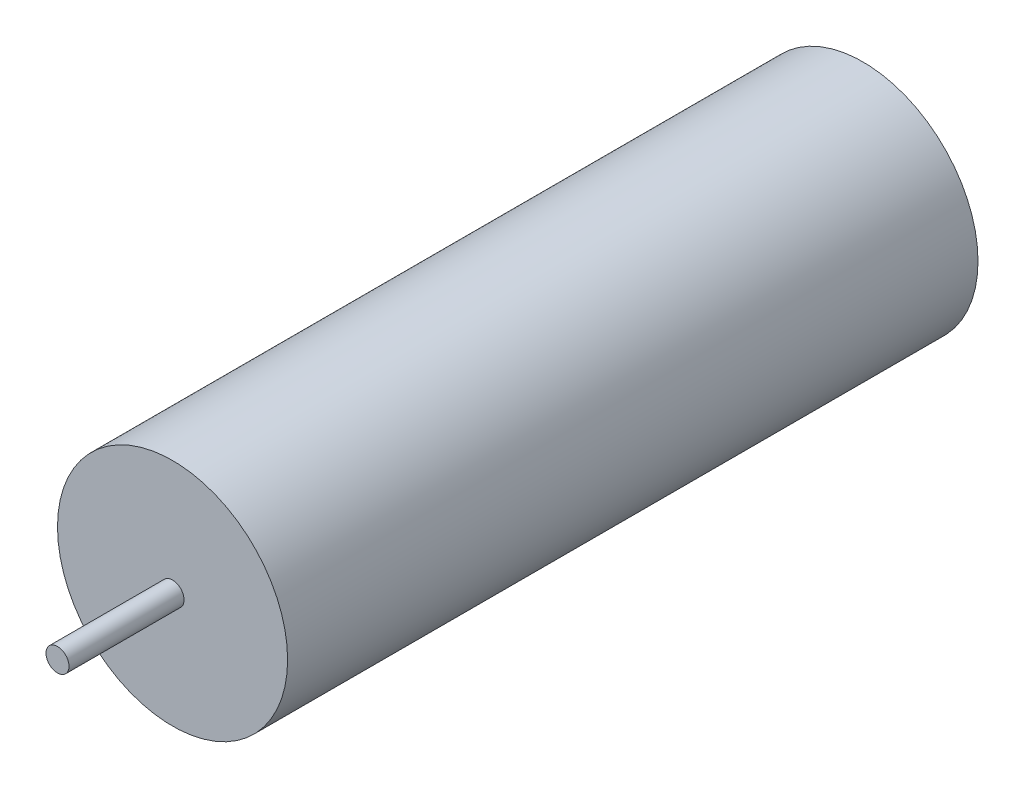
SolidWorks part; units mm, degrees
material "1023 Carbon Steel Sheet (SS)"
ref_plane "Front Plane" through (0, 0, 0) normal (0, 0, 1) x (1, 0, 0)
ref_plane "Top Plane" through (0, 0, 0) normal (0, 1, 0) x (1, 0, 0)
ref_plane "Right Plane" through (0, 0, 0) normal (1, 0, 0) x (0, 0, -1)
sketch "Sketch1" plane through (0, 0, 0) normal (0, 0, 1) x (1, 0, 0)
  circle A0 centre (0, -25.4) radius 12.7
  dimension "D1" = 25.4
extrude "Boss-Extrude1" add sketch "Sketch1" against normal blind 76.2
sketch "Sketch2" plane through (0, 0, 0) normal (0, 0, 1) x (1, 0, 0)
  circle A0 centre (0, -25.4) radius 1.27
  dimension "D1" = 2.54
extrude "Boss-Extrude2" add sketch "Sketch2" along normal blind 12.7
